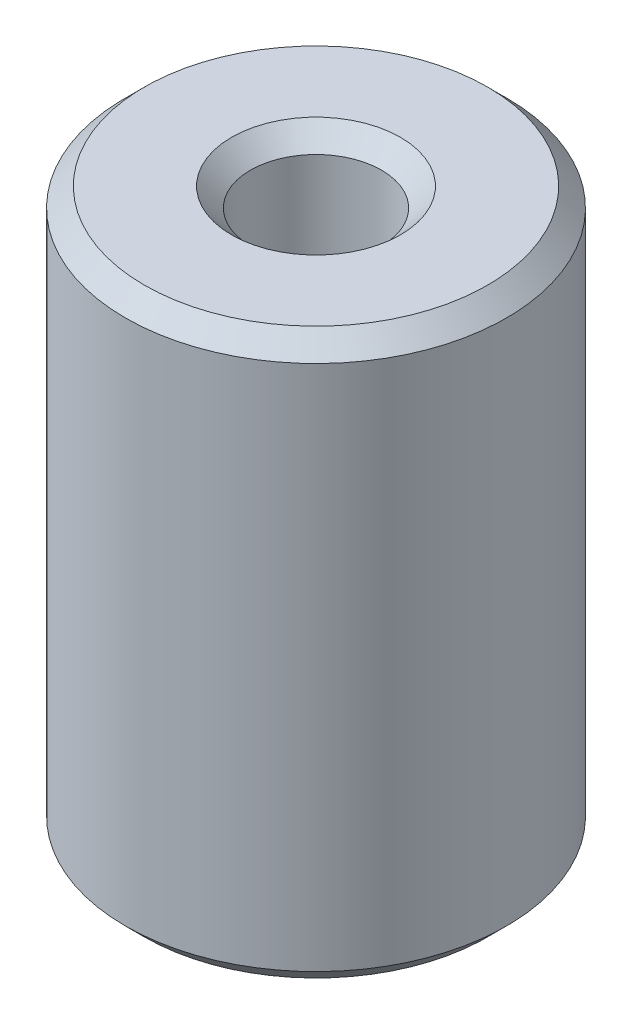
SolidWorks part; units mm, degrees
ref_plane "Front Plane" through (0, 0, 0) normal (0, 0, 1) x (1, 0, 0)
ref_plane "Top Plane" through (0, 0, 0) normal (0, 1, 0) x (1, 0, 0)
ref_plane "Right Plane" through (0, 0, 0) normal (1, 0, 0) x (0, 0, -1)
sketch "Sketch1" plane through (0, 0, 0) normal (0, 1, 0) x (1, 0, 0)
  circle A0 centre (0, 0) radius 7.5
  dimension "SLEEVE_OD" = 15
extrude "Boss-Extrude1" add sketch "Sketch1" along normal blind 22.2179
sketch "Sketch2" plane through (0, 0, 0) normal (0, 1, 0) x (1, 0, 0)
  circle A0 centre (0, 0) radius 2.5795
  dimension "BORE_D" = 5.1589
extrude "Cut-Extrude1" cut sketch "Sketch2" along normal through all
chamfer "Chamfer1" distance 0.7457 angle 45 4 edges at (0, 22.2179, 2.5795) (0, 0, 2.5795) (0, 0, 7.5) (0, 22.2179, 7.5)
